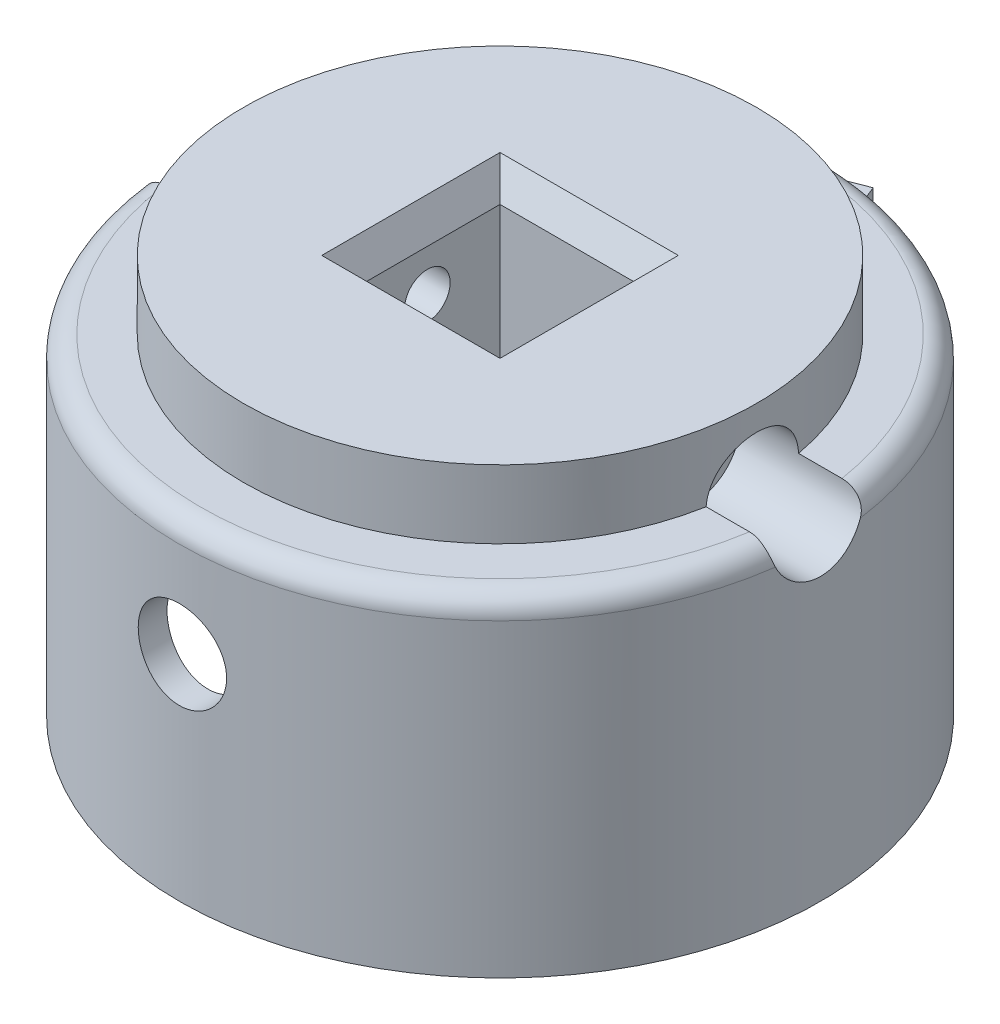
SolidWorks part; units mm, degrees
ref_plane "Спереди" through (0, 0, 0) normal (0, 0, 1) x (1, 0, 0)
ref_plane "Сверху" through (0, 0, 0) normal (0, 1, 0) x (1, 0, 0)
ref_plane "Справа" through (0, 0, 0) normal (1, 0, 0) x (0, 0, -1)
sketch "Sketch1" plane through (0, 0, 0) normal (0, 1, 0) x (1, 0, 0)
  circle A0 centre (0, 0) radius 22.5
  dimension "D1" = 45
extrude "Boss-Extrude1" add sketch "Sketch1" along normal blind 28
sketch "Sketch2" plane through (0, 0, 0) normal (0, -1, 0) x (1, 0, 0)
  line L1 (5.1, 5.1) -> (-5.1, 5.1)
  line L2 (5.1, 5.1) -> (5.1, -5.1)
  line L3 (5.1, -5.1) -> (-5.1, -5.1)
  line L4 (-5.1, 5.1) -> (-5.1, -5.1)
  line L5 (5.1, 5.1) -> (-5.1, -5.1) construction
  line L6 (5.1, -5.1) -> (-5.1, 5.1) construction
  point P0 (0, 0)
  dimension "D1" = 10.2
extrude "Cut-Extrude2" cut sketch "Sketch2" against normal through all
shell "Shell3" thickness 2 removed face at (0, 0, 0)
sketch "Sketch3" plane through (0, 0, 7.1) normal (0, 0, 1) x (1, 0, 0)
  line L0 (0, 26) -> (0, 0) construction
  line L1 (7.1, 26) -> (-7.1, 26) construction
  line L2 (7.1, 0) -> (-7.1, 0) construction
  line L3 (-22.5, 0) -> (22.5, 0) construction
  circle A0 centre (0, 15) radius 3.1
  dimension "D1" = 6.2
  dimension "D2" = 15
extrude "Cut-Extrude3" cut sketch "Sketch3" along normal through all
chamfer "Chamfer1" distance 2 angle 30 4 edges at (-5.1, 28, 0) (0, 28, 5.1) (5.1, 28, 0) (0, 28, -5.1) first distance on face at (-5.1, 14, 0) first distance on face at (0, 14, 5.1) first distance on face at (5.1, 14, 0) first distance on face at (0, 14, -5.1)
sketch "Sketch18" plane through (0, 26, 0) normal (0, -1, 0) x (1, 0, 0)
  line L0 (0, 0) -> (-18.4253, -8.9866) construction
  line L1 (0, 0) -> (-17.385, 10.8633) construction
  line L2 (0, 0) -> (0, -20.5) construction
  line L3 (-15.7289, -7.6715) -> (-18.4253, -8.9866)
  line L4 (-14.8408, 9.2736) -> (-17.385, 10.8633)
  circle A0 centre (0, 0) radius 20.5 construction
  arc A1 (-18.4253, -8.9866) -> (-17.385, 10.8633) centre (0, 0) cw
  arc A2 (-14.8408, 9.2736) -> (-15.7289, -7.6715) centre (0, 0) ccw
  dimension "D1" = 64
  dimension "D2" = 58
  dimension "D3" = 3
extrude "Boss-Extrude8" add sketch "Sketch18" along normal offset from surface (23 mm away) 3 up to face at (0, 0, 20.5)
sketch "Sketch9" plane through (0, 0, 0) normal (0, -1, 0) x (1, 0, 0)
  line L0 (0, -7.1) -> (0, -20.5) construction
  line L2 (2.0637, -22.4052) -> (-16.5922, -15.197)
  line L3 (-16.5922, -15.197) -> (-17.6734, -17.9954)
  line L4 (-17.6734, -17.9954) -> (0.9825, -25.2035)
  line L5 (0.9825, -25.2035) -> (2.0637, -22.4052)
  line L6 (-7.1, -7.1) -> (7.1, -7.1) construction
  line L7 (2.0637, -22.4052) -> (0, -7.1) construction
  circle A0 centre (0, 0) radius 22.5 construction
  circle A1 centre (0, 0) radius 20.5 construction
  dimension "D1" = 20
  dimension "D2" = 3
  dimension "D3" = 7.679
extrude "Boss-Extrude4" add sketch "Sketch9" against normal blind 20
sketch "Sketch11" plane through (0, 0, 0) normal (0, -1, 0) x (1, 0, 0)
  line L0 (2.0637, -22.4052) -> (7.1, -7.1)
  line L1 (7.1, -7.1) -> (-7.1, -7.1)
  line L2 (-7.1, -7.1) -> (-16.5922, -15.197)
  line L3 (-16.5922, -15.197) -> (2.0637, -22.4052) construction
  line L4 (-3.774, -20.1496) -> (-10.7544, -17.4526) construction
  arc A0 (2.0637, -22.4052) -> (-16.5922, -15.197) centre (0, 0) ccw construction
  arc A1 (2.0637, -22.4052) -> (-16.5922, -15.197) centre (0, 0) cw
  arc A2 (2.0637, -22.4052) -> (-16.5922, -15.197) centre (0, 0) ccw construction
  point P4 (-7.2642, -18.8011)
extrude "Boss-Extrude6" add sketch "Sketch11" against normal up to surface (26 mm away) up to face at (0, 26, 0)
sketch "Sketch12" plane through (0, 0, 0) normal (0, -1, 0) x (1, 0, 0)
  line L0 (-7.1, -7.1) -> (-15.0695, -13.8982) construction
  line L1 (2.7517, -20.3145) -> (7.1, -7.1) construction
  line L2 (3.8154, -17.0817) -> (2.7517, -20.3145)
  line L3 (-15.0695, -13.8982) -> (-12.7871, -11.9512)
  arc A0 (2.7517, -20.3145) -> (-15.0695, -13.8982) centre (0, 0) cw
  arc A1 (-12.7871, -11.9512) -> (3.8154, -17.0817) centre (0, 0) ccw
  arc A2 (2.7517, -20.3145) -> (-15.0695, -13.8982) centre (0, 0) ccw construction
  dimension "D1" = 3
extrude "Cut-Extrude5" cut sketch "Sketch12" against normal blind 12
sketch "Sketch13" plane through (-8.3455, 0, -21.5995) normal (-0.3604, 0, -0.9328) x (-0.9328, 0, 0.3604)
  line L0 (0, 20) -> (0, 0) construction
  line L1 (10, 20) -> (-10, 20) construction
  line L2 (10, 0) -> (-10, 0) construction
  circle A0 centre (0, 10) radius 3.8
  dimension "D1" = 7.6
extrude "Cut-Extrude6" cut sketch "Sketch13" against normal blind 16
sketch "Sketch15" plane through (-8.3455, 0, -21.5995) normal (-0.3604, 0, -0.9328) x (-0.9328, 0, 0.3604)
  line L0 (-10, 10) -> (10, 10) construction
  line L1 (-10, 20) -> (-10, 0) construction
  line L2 (10, 20) -> (10, 0) construction
  line L4 (5, 11.5) -> (-5, 11.5)
  line L5 (5, 11.5) -> (5, 8.5)
  line L6 (5, 8.5) -> (-5, 8.5)
  line L7 (-5, 11.5) -> (-5, 8.5)
  line L8 (5, 11.5) -> (-5, 8.5) construction
  line L9 (5, 8.5) -> (-5, 11.5) construction
  point P6 (0, 10)
  dimension "D1" = 10
  dimension "D2" = 3
extrude "Cut-Extrude8" cut sketch "Sketch15" against normal blind 16
sketch "Sketch17" plane through (0, 0, 0) normal (0, -1, 0) x (1, 0, 0)
  line L0 (7.1, 7.1) -> (7.1, -7.1)
  line L1 (7.1, -7.1) -> (3.8154, -17.0817)
  line L2 (7.1, 7.1) -> (-7.1, 7.1)
  line L3 (-7.1, 7.1) -> (-7.1, -7.1)
  line L4 (-7.1, -7.1) -> (-12.7871, -11.9512)
  arc A0 (3.8154, -17.0817) -> (-12.7871, -11.9512) centre (0, 0) cw
  arc A1 (-12.7871, -11.9512) -> (3.8154, -17.0817) centre (0, 0) ccw construction
extrude "Cut-Extrude9" cut sketch "Sketch17" against normal blind 2
sketch "Sketch20" plane through (0, 26, 0) normal (0, -1, 0) x (1, 0, 0)
  line L0 (2.7517, -20.3145) -> (7.1, -7.1)
  line L1 (7.1, -7.1) -> (7.1, 7.1)
  line L2 (7.1, 7.1) -> (-7.1, 7.1)
  line L3 (-7.1, 7.1) -> (-7.1, -7.1)
  line L4 (-7.1, -7.1) -> (-15.0695, -13.8982)
  arc A0 (2.7517, -20.3145) -> (-15.0695, -13.8982) centre (0, 0) ccw
  arc A1 (2.7517, -20.3145) -> (-17.385, 10.8633) centre (0, 0) ccw construction
extrude "Boss-Extrude10" add sketch "Sketch20" along normal blind 7
sketch "Sketch21" plane through (0, 28, 0) normal (0, 1, 0) x (1, 0, 0)
  circle A0 centre (0, 0) radius 18
  dimension "D1" = 36
extrude "Cut-Extrude11" cut sketch "Sketch21" against normal blind 4.8 flip side to cut
sketch "Sketch22" plane through (5.1, 0, 0) normal (-1, 0, 0) x (0, 0, 1)
  line L0 (0, 26) -> (0, 2) construction
  line L1 (5.1, 26) -> (-5.1, 26) construction
  line L2 (-5.1, 2) -> (5.1, 2) construction
  line L3 (-6.2547, 28) -> (6.2547, 28) construction
  circle A0 centre (0, 23) radius 1.6
  point P10 (0, 28)
  dimension "D1" = 3.2
  dimension "D2" = 5
extrude "Cut-Extrude12" cut sketch "Sketch22" against normal through all both and the other way through all
sketch "Sketch24" plane through (5.1, 0, 0) normal (-1, 0, 0) x (0, 0, 1)
  circle A0 centre (0, 23) radius 3.25
  dimension "D1" = 6.5
extrude "Cut-Extrude13" cut sketch "Sketch24" against normal through all from offset 8.5 offset against normal yes
sketch "Sketch25" plane through (-5.1, 0, 0) normal (1, 0, 0) x (0, 0, -1)
  line L0 (-5.1, 26) -> (-5.1, 2) construction
  line L1 (0, 19.8936) -> (2.6903, 21.4468)
  line L2 (2.6903, 21.4468) -> (2.6903, 24.5532)
  line L3 (2.6903, 24.5532) -> (0, 26.1064)
  line L4 (0, 26.1064) -> (-2.6903, 24.5532)
  line L5 (-2.6903, 24.5532) -> (-2.6903, 21.4468)
  line L6 (-2.6903, 21.4468) -> (0, 19.8936)
  circle A0 centre (0, 23) radius 3.1064 construction
extrude "Cut-Extrude14" cut sketch "Sketch25" against normal through all from offset 8.5 offset against normal yes
fillet "Fillet1" radius 1.5 2 edges at (-0.2792, 23.2, 22.4983) (-0.2792, 23.2, -22.4983)
